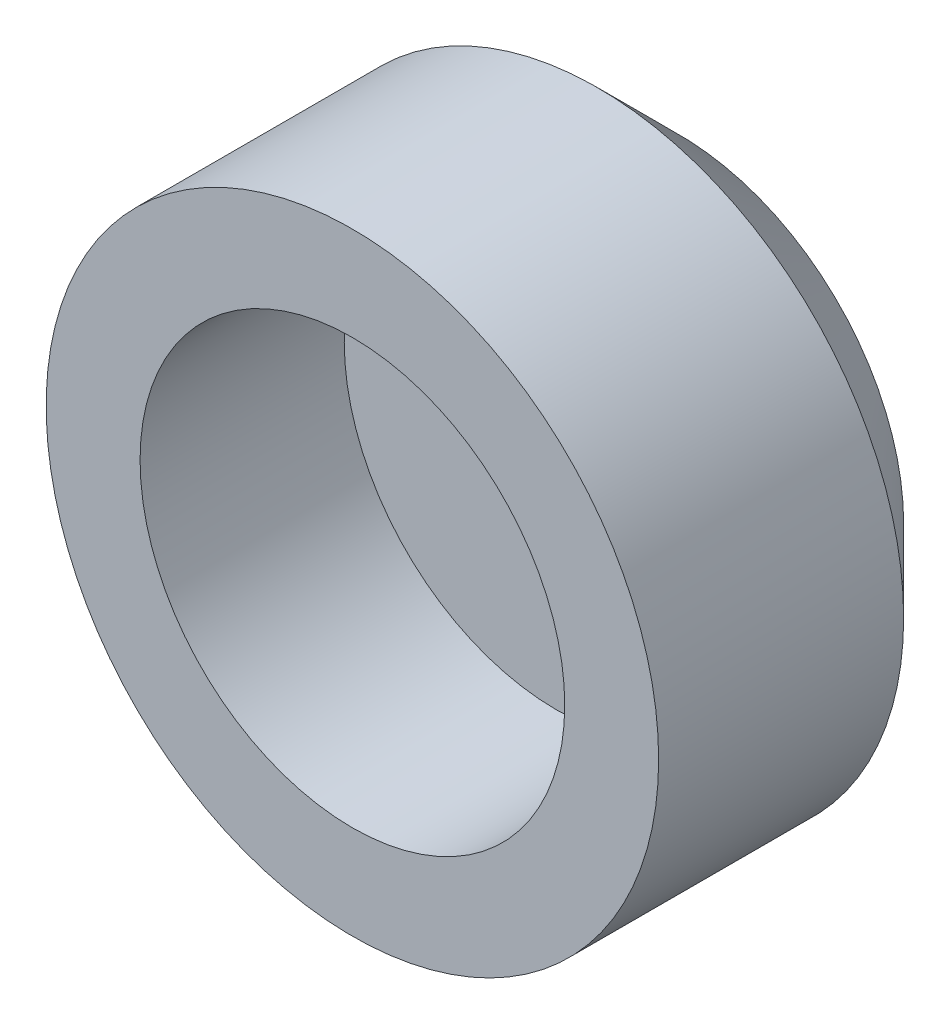
SolidWorks part; units mm, degrees
ref_plane "Front Plane" through (0, 0, 0) normal (0, 0, 1) x (1, 0, 0)
ref_plane "Top Plane" through (0, 0, 0) normal (0, 1, 0) x (1, 0, 0)
ref_plane "Right Plane" through (0, 0, 0) normal (1, 0, 0) x (0, 0, -1)
sketch "Sketch1" plane through (0, 0, 0) normal (0, 0, 1) x (1, 0, 0)
  circle A0 centre (0, 0) radius 3.75
  circle A1 centre (0, 0) radius 2.6
  dimension "D1" = 5.2
  dimension "D2" = 7.5
extrude "Boss-Extrude1" add sketch "Sketch1" along normal blind 1.5 contours A1
extrude "Boss-Extrude2" add sketch "Sketch1<3>" along normal blind 4
sketch "Sketch1<3>" plane through (0, 0, 0) normal (0, 0, 1) x (1, 0, 0) same geometry as "Sketch1"
chamfer "Chamfer1" distance 1 angle 45 1 edges at (3.75, 0, 0)
